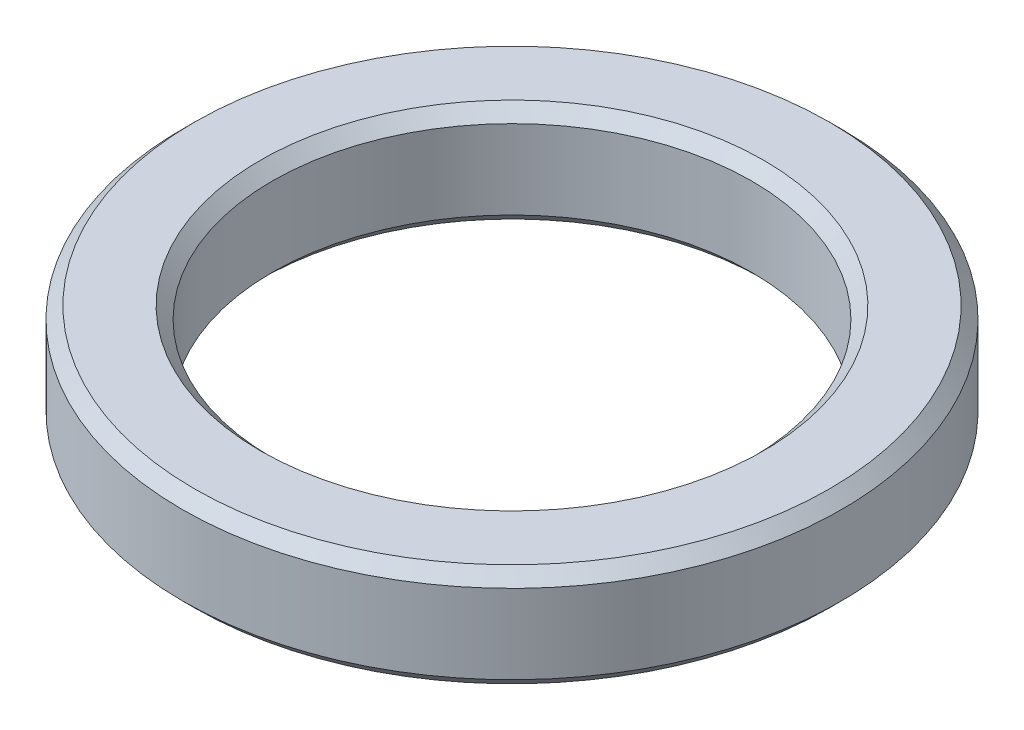
SolidWorks part; units mm, degrees
ref_plane "Ebene vorne" through (0, 0, 0) normal (0, 0, 1) x (1, 0, 0)
ref_plane "Ebene oben" through (0, 0, 0) normal (0, 1, 0) x (1, 0, 0)
ref_plane "Ebene rechts" through (0, 0, 0) normal (1, 0, 0) x (0, 0, -1)
sketch "Skizze1" plane through (0, 0, 0) normal (0, 1, 0) x (1, 0, 0)
  circle A0 centre (0, 0) radius 2
  circle A1 centre (0, 0) radius 2.75
  dimension "D1" = 4
  dimension "D2" = 5.5
extrude "Aufsatz-Linear austragen1" add sketch "Skizze1" along normal blind 0.86
chamfer "Fase1" distance 0.1 angle 45 4 edges at (0, 0, 2) (0, 0, 2.75) (0, 0.86, 2) (0, 0.86, 2.75)
ref_axis "Achse1" through (0, -0.043, 0) along (0, 1, 0)
